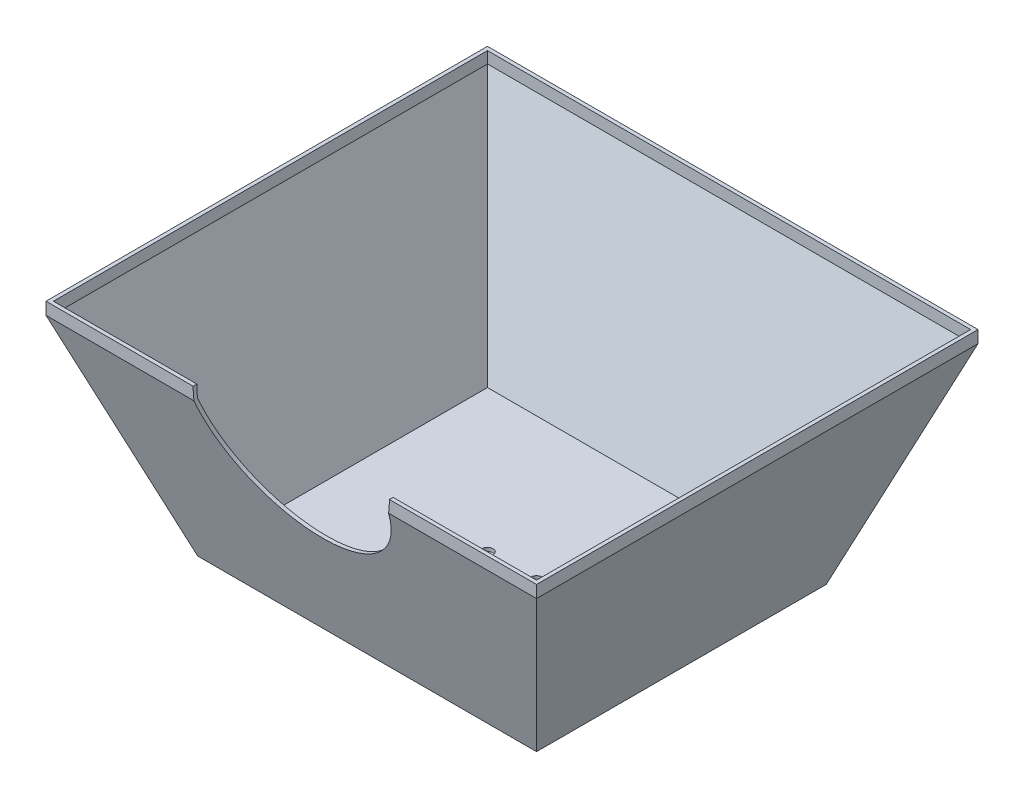
SolidWorks part; units mm, degrees
ref_plane "Front Plane" through (0, 0, 0) normal (0, 0, 1) x (1, 0, 0)
ref_plane "Top Plane" through (0, 0, 0) normal (0, 1, 0) x (1, 0, 0)
ref_plane "Right Plane" through (0, 0, 0) normal (1, 0, 0) x (0, 0, -1)
sketch "Sketch1" plane through (0, 0, 0) normal (0, 1, 0) x (1, 0, 0)
  line L1 (0, 0) -> (200, 0)
  line L2 (0, 0) -> (0, 180)
  line L3 (0, 180) -> (200, 180)
  line L4 (200, 0) -> (200, 180)
  dimension "D1" = 200
  dimension "D2" = 180
extrude "Boss-Extrude1" add sketch "Sketch1" along normal blind 90
sketch "Sketch4" plane through (0, 0, 0) normal (0, 0, 1) x (1, 0, 0)
  line L0 (0, 85) -> (30.9375, 0)
  line L1 (0, 90) -> (0, 0) construction
  line L2 (0, 0) -> (200, 0) construction
  line L3 (100, 90) -> (100, 0) construction
  line L4 (0, 90) -> (200, 90) construction
  line L5 (0, 85) -> (0, 0)
  line L6 (0, 0) -> (30.9375, 0)
  line L7 (200, 85) -> (200, 0)
  line L8 (200, 85) -> (169.0625, 0)
  line L9 (200, 0) -> (169.0625, 0)
  dimension "D1" = 5
  dimension "D2" = 70
extrude "Cut-Extrude1" cut sketch "Sketch4" against normal through all and the other way through all contours L6 L0 L5 | L7 L9 L8
sketch "Sketch5" plane through (0, 0, 0) normal (-1, 0, 0) x (0, 0, 1)
  line L0 (-180, 85) -> (-149.0625, 0)
  line L1 (-180, 85) -> (-180, 0) construction
  line L2 (-180, 0) -> (0, 0) construction
  line L3 (-90, 90) -> (-90, 0) construction
  line L4 (-180, 90) -> (0, 90) construction
  line L5 (-180, 85) -> (-180, 0)
  line L6 (-180, 0) -> (-149.0625, 0)
  line L7 (0, 85) -> (-30.9375, 0)
  line L8 (0, 85) -> (0, 0)
  line L9 (0, 0) -> (-30.9375, 0)
  dimension "D1" = 5
  dimension "D2" = 70
extrude "Cut-Extrude2" cut sketch "Sketch5" against normal through all contours L6 L0 L5 | L7 L9 L8
shell "Shell1" thickness 1.5 removed face at (100, 90, -90)
sketch "Sketch6" plane through (0, 1.5, 0) normal (0, 1, 0) x (1, 0, 0)
  line L0 (168.0122, 148.0122) -> (168.0122, 31.9878) construction
  line L1 (168.0122, 31.9878) -> (31.9878, 31.9878) construction
  line L2 (31.9878, 148.0122) -> (31.9878, 31.9878) construction
  line L3 (168.0122, 148.0122) -> (31.9878, 148.0122) construction
  line L4 (168.0122, 148.0122) -> (168.0122, 31.9878)
  line L5 (168.0122, 31.9878) -> (31.9878, 31.9878)
  line L6 (31.9878, 148.0122) -> (31.9878, 31.9878)
  line L7 (168.0122, 148.0122) -> (31.9878, 148.0122)
  line L8 (31.9878, 90) -> (168.0122, 90) construction
  line L9 (100, 148.0122) -> (100, 31.9878) construction
  circle A0 centre (90, 90) radius 2.25
  circle A2 centre (110, 90) radius 2.25
  point P11 (100, 90)
  point P13 (100, 90)
  dimension "D2" = 4.5
  dimension "D1" = 10
extrude "Hinge-Holes" cut sketch "Sketch6" against normal through all contours A0 | A2
sketch "Sketch7" plane through (0, 0, 0) normal (0, 0, 1) x (1, 0, 0)
  line L0 (0, 90) -> (200, 90) construction
  line L1 (0, 90) -> (200, 90)
  line L2 (60, 90) -> (140, 90)
  arc A0 (60, 90) -> (140, 90) centre (100, 90) ccw
  point P6 (100, 90)
  line M2 (0, 85) -> (200, 85)
  dimension "D1" = 40
extrude "Cut-Extrude4" cut sketch "Sketch7" against normal blind 50 contours A0 M2 | L1 A0 M2 region at (100, 87.5033, 0) region at (100, 70.2912, 0)
